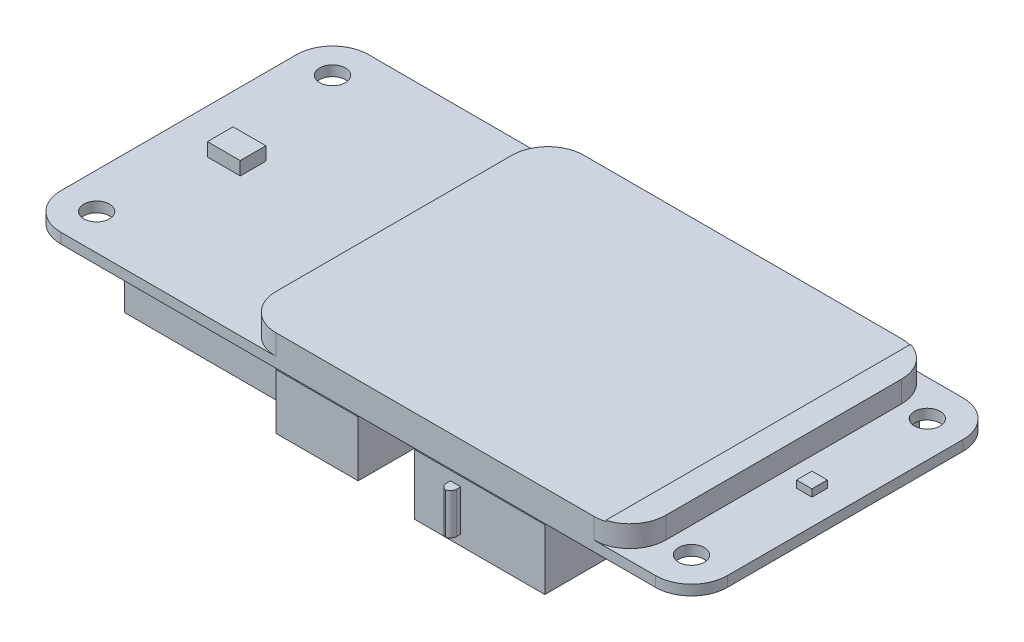
SolidWorks part; units mm, degrees
ref_plane "前视基准面" through (0, 0, 0) normal (0, 0, 1) x (1, 0, 0)
ref_plane "上视基准面" through (0, 0, 0) normal (0, 1, 0) x (1, 0, 0)
ref_plane "右视基准面" through (0, 0, 0) normal (1, 0, 0) x (0, 0, -1)
other "Configuration Table"
sketch "草图1" plane through (0, 0, 0) normal (0, 1, 0) x (1, 0, 0)
  line L1 (-29, 15) -> (29, 15)
  line L2 (-32.5, 11.5) -> (-32.5, -11.5)
  line L3 (-29, -15) -> (29, -15)
  line L4 (32.5, 11.5) -> (32.5, -11.5)
  line L5 (-32.5, 15) -> (32.5, -15) construction
  line L6 (-32.5, -15) -> (32.5, 15) construction
  arc A0 (29, -15) -> (32.5, -11.5) centre (29, -11.5) ccw
  arc A1 (29, 15) -> (32.5, 11.5) centre (29, 11.5) cw
  arc A2 (-32.5, -11.5) -> (-29, -15) centre (-29, -11.5) ccw
  arc A3 (-29, 15) -> (-32.5, 11.5) centre (-29, 11.5) ccw
  circle A4 centre (-29, 11.5) radius 1.25
  circle A5 centre (29, 11.5) radius 1.25
  circle A6 centre (-29, -11.5) radius 1.25
  circle A7 centre (29, -11.5) radius 1.25
  point P0 (0, 0)
  dimension "D3" = 3.5
  dimension "D4" = 2.5
  dimension "D1" = 65
  dimension "D2" = 30
extrude "board" add sketch "草图1" along normal blind 1
sketch "草图2" plane through (0, 1, 0) normal (0, 1, 0) x (1, 0, 0)
  line L0 (29, 15) -> (-29, 15) construction
  line L1 (-11.5, 15) -> (26.5, 15)
  line L2 (-11.5, 15) -> (-11.5, -15)
  line L3 (-11.5, -15) -> (26.5, -15)
  line L4 (26.5, 15) -> (26.5, -15)
  line L5 (-29, -15) -> (29, -15) construction
  line L6 (-32.5, 11.5) -> (-32.5, -11.5) construction
  line L7 (32.5, -11.5) -> (32.5, 11.5) construction
  dimension "D1" = 6
  dimension "D2" = 21
extrude "screen" add sketch "草图2" along normal blind 2
fillet "screen-radius" radius 3.5 4 edges at (-11.5, 2, -15) (26.5, 2, -15) (26.5, 2, 15) (-11.5, 2, 15)
sketch "草图9" plane through (0, 3, 0) normal (0, 1, 0) x (1, 0, 0)
  line L0 (26.5, -11.5) -> (26.5, 11.5) construction
  line L1 (26.5, -11.5) -> (26.5, 11.5)
  line L2 (24, 14.8541) -> (24, -14.8541)
  line L3 (32.5, -11.5) -> (32.5, 11.5) construction
  arc A0 (23, -15) -> (26.5, -11.5) centre (23, -11.5) ccw construction
  arc A1 (26.5, 11.5) -> (23, 15) centre (23, 11.5) ccw construction
  arc A2 (26.5, -11.5) -> (24, -14.8541) centre (23, -11.5) cw
  arc A3 (26.5, 11.5) -> (24, 14.8541) centre (23, 11.5) ccw
  dimension "D1" = 8.5
extrude "screen-top" add sketch "草图9" along normal blind 0.1
sketch "草图3" plane through (0, 0, 0) normal (0, -1, 0) x (1, 0, 0)
  line L0 (32.5, 11.5) -> (32.5, -11.5) construction
  line L1 (-25.5, -9.25) -> (25.5, -9.25)
  line L2 (-25.5, -9.25) -> (-25.5, -14.25)
  line L3 (-25.5, -14.25) -> (25.5, -14.25)
  line L4 (25.5, -9.25) -> (25.5, -14.25)
  line L6 (29, -15) -> (-29, -15) construction
  dimension "D1" = 5
  dimension "D2" = 51
  dimension "D3" = 7
  dimension "D4" = 0.75
extrude "plug" add sketch "草图3" along normal blind 5.2
sketch "草图4" plane through (0, 0, 0) normal (0, -1, 0) x (1, 0, 0)
  line L1 (-25.09, 12.68) -> (-9.95, 12.68)
  line L2 (-25.09, 12.68) -> (-25.09, -7.32)
  line L3 (-25.09, -7.32) -> (-9.95, -7.32)
  line L4 (-9.95, 12.68) -> (-9.95, -7.32)
  line L5 (-32.5, -11.5) -> (-32.5, 11.5) construction
  line L6 (-29, 15) -> (29, 15) construction
  dimension "D1" = 15.14
  dimension "D2" = 20
  dimension "D3" = 7.41
  dimension "D4" = 2.32
extrude "speaker" add sketch "草图4" along normal blind 5
sketch "草图10" plane through (0, 0, 0) normal (0, -1, 0) x (1, 0, 0)
  line L0 (-29, 15) -> (29, 15) construction
  line L1 (-8, 15) -> (0, 15)
  line L2 (-8, 15) -> (-8, 9)
  line L3 (-8, 9) -> (0, 9)
  line L4 (0, 15) -> (0, 9)
  line L5 (-32.5, -11.5) -> (-32.5, 11.5) construction
  dimension "D1" = 8
  dimension "D2" = 6
  dimension "D3" = 24.5
extrude "speaker2plug" add sketch "草图10" along normal blind 5.5
sketch "草图5" plane through (0, 0, 0) normal (0, -1, 0) x (1, 0, 0)
  line L1 (5.5, 15) -> (18.2, 15)
  line L2 (5.5, 15) -> (5.5, 9)
  line L3 (5.5, 9) -> (18.2, 9)
  line L4 (18.2, 15) -> (18.2, 9)
  line L5 (-29, 15) -> (-8, 15) construction
  line L6 (32.5, 11.5) -> (32.5, -11.5) construction
  dimension "D1" = 12.7
  dimension "D2" = 6
  dimension "D4" = 14.3
extrude "button" add sketch "草图5" along normal blind 6
sketch "草图6" plane through (0, 0, 15) normal (0, 0, 1) x (1, 0, 0)
  line L1 (18.2, -6) -> (5.5, -6) construction
  line L3 (9, -1) -> (10, -1)
  line L4 (9, -1) -> (9, -5)
  line L5 (9, -5) -> (10, -5)
  line L6 (10, -1) -> (10, -5)
  line L7 (-29, 0) -> (-8, 0) construction
  dimension "D2" = 1
  dimension "D3" = 1
  dimension "D4" = 1
extrude "button-tap" add sketch "草图6" along normal blind 1
fillet "tap-radius " radius 0.6 2 edges at (10, -3, 16) (9, -3, 16)
sketch "草图7" plane through (0, 1, 0) normal (0, 1, 0) x (1, 0, 0)
  line L1 (28.5, 0.75) -> (30, 0.75)
  line L2 (28.5, 0.75) -> (28.5, -0.75)
  line L3 (28.5, -0.75) -> (30, -0.75)
  line L4 (30, 0.75) -> (30, -0.75)
  line L6 (32.5, -11.5) -> (32.5, 11.5) construction
  point P4 (32.5, 0)
  point P5 (30, 0)
  dimension "D1" = 1.5
  dimension "D2" = 1.5
  dimension "D4" = 2.5
extrude "rgb-led" add sketch "草图7" along normal blind 0.7
sketch "草图8" plane through (0, 1, 0) normal (0, 1, 0) x (1, 0, 0)
  line L0 (29, 15) -> (23, 15) construction
  line L1 (-25, 1) -> (-28.2, 1)
  line L2 (-25, 1) -> (-25, -1.5)
  line L3 (-25, -1.5) -> (-28.2, -1.5)
  line L4 (-28.2, 1) -> (-28.2, -1.5)
  line L6 (-32.5, 11.5) -> (-32.5, -11.5) construction
  dimension "D1" = 3.2
  dimension "D2" = 2.5
  dimension "D3" = 14
  dimension "D4" = 4.3
extrude "mic" add sketch "草图8" along normal blind 1.3
sketch "草图11" plane through (0, 0, 15) normal (0, 0, 1) x (1, 0, 0)
  line L0 (18.2, -6) -> (18.2, 0) construction
  line L1 (-8, 0) -> (18.2, 0)
  line L2 (-8, 0) -> (-8, -0.1)
  line L3 (-8, -0.1) -> (18.2, -0.1)
  line L4 (18.2, 0) -> (18.2, -0.1)
  line L5 (-8, -5.5) -> (-8, 0) construction
  dimension "D1" = 0.1
extrude "split" cut sketch "草图11" against normal blind 1
